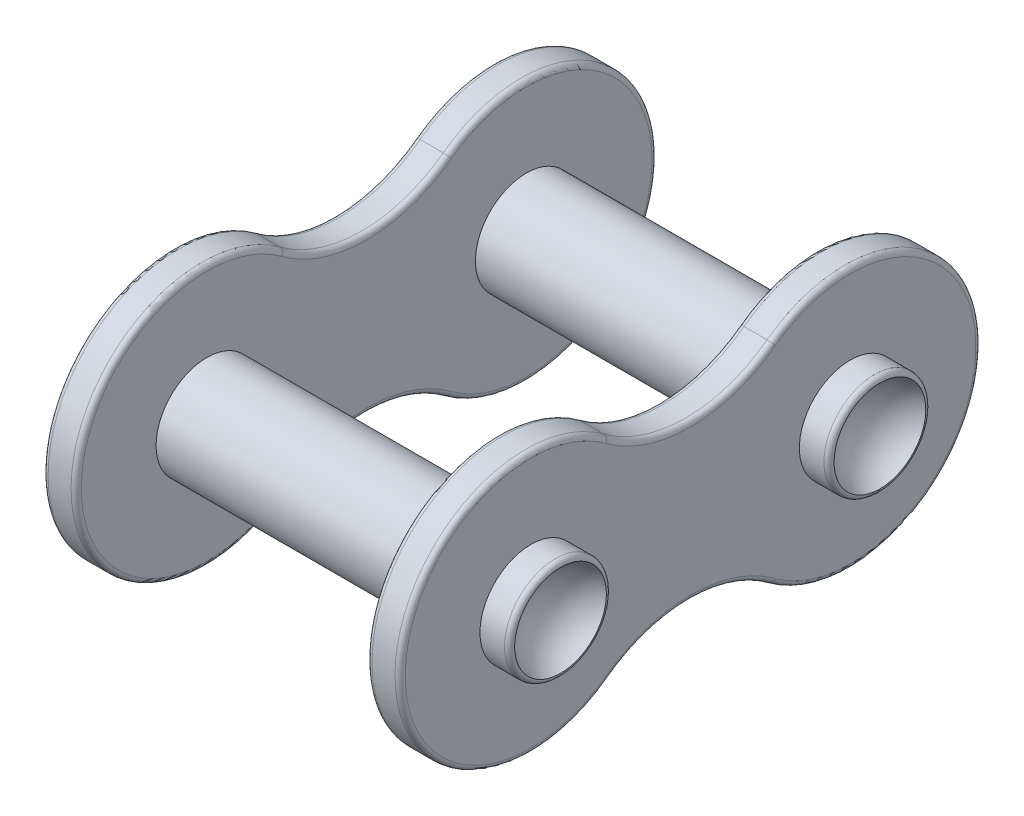
SolidWorks part; units mm, degrees
material "AISI 304"
ref_plane "Front Plane" through (0, 0, 0) normal (0, 0, 1) x (1, 0, 0)
ref_plane "Top Plane" through (0, 0, 0) normal (0, 1, 0) x (1, 0, 0)
ref_plane "Right Plane" through (0, 0, 0) normal (1, 0, 0) x (0, 0, -1)
sketch "Sketch2" plane through (0, 0, 0) normal (1, 0, 0) x (0, 0, -1)
  line L0 (0, 11.3944) -> (0, -10.9786) construction
  line L1 (-13.8367, 0) -> (19.9695, 0) construction
  circle A0 centre (7.9375, 0) radius 2.53
  arc A1 (4.0585, -5.2157) -> (4.0585, 5.2157) centre (7.9375, 0) ccw
  arc A2 (-4.0585, -5.2157) -> (-4.0585, 5.2157) centre (-7.9375, 0) cw
  circle A3 centre (-7.9375, 0) radius 2.53
  arc A4 (-4.0585, 5.2157) -> (4.0585, 5.2157) centre (0, 10.6726) ccw
  arc A5 (-4.0585, -5.2157) -> (4.0585, -5.2157) centre (0, -10.6726) cw
  dimension "D1" = 13
  dimension "D2" = 5.06
  dimension "D3" = 7.9375
extrude "Boss-Extrude1" add sketch "Sketch2" along normal blind 1.65
sketch "Sketch3" plane through (1.65, 0, 0) normal (1, 0, 0) x (0, 0, -1)
  circle A0 centre (7.9375, 0) radius 2.53 construction
  circle A1 centre (7.9375, 0) radius 2.53
extrude "Boss-Extrude2" add sketch "Sketch3" along normal blind 1.475 and the other way blind 19.225
ref_plane "Plane1" through (-7.225, 0, 0) normal (1, 0, 0) x (0, 0, -1)
mirror "Mirror1" about plane through (-7.225, 0, 0) normal (1, 0, 0) of "Boss-Extrude1"
sketch "Sketch5" plane through (0, 0, 0) normal (0, 1, 0) x (1, 0, 0)
  line L0 (-16.1, 7.9375) -> (-19.1, 7.9375) construction
  line L1 (-16.1, 10.4675) -> (-16.1, 5.4075) construction
  line L2 (-16.1, 7.9375) -> (-17.6, 7.9375)
  line L3 (-17.6, 7.9375) -> (-17.6, 10.2288)
  arc A0 (-16.1, 7.9375) -> (-17.6, 10.2288) centre (-18.6, 7.9375) ccw
  dimension "D1" = 2.5
  dimension "D2" = 1.5
revolve "Cut-Revolve1" cut sketch "Sketch5" angle 360 about L0
mirror "Mirror2" about plane through (0, 0, 0) normal (0, 0, 1) of "Boss-Extrude2"
mirror "Mirror3" about plane through (0, 0, 0) normal (0, 0, 1) of "Cut-Revolve1"
mirror "Mirror4" about plane through (-7.225, 0, 0) normal (1, 0, 0) of "Mirror3"
fillet "Fillet1" radius 0.254 4 edges at (3.125, 0, 10.4675) (3.125, 0, -10.4675) (-17.575, 0, 10.4675) (-17.575, 0, -10.4675)
fillet "Fillet2" radius 0.254 16 edges at (1.65, 3.8719, 0) (1.65, 0, -14.4375) (1.65, -3.8719, 0) (0, 3.8719, 0) (0, 0, -14.4375) (0, -3.8719, 0) (-16.1, 3.8719, 0) (-16.1, 0, -14.4375) (-16.1, -3.8719, 0) (-14.45, 3.8719, 0) (-14.45, 0, -14.4375) (-14.45, -3.8719, 0) (1.65, 0, 14.4375) (0, 0, 14.4375) (-16.1, 0, 14.4375) (-14.45, 0, 14.4375)
